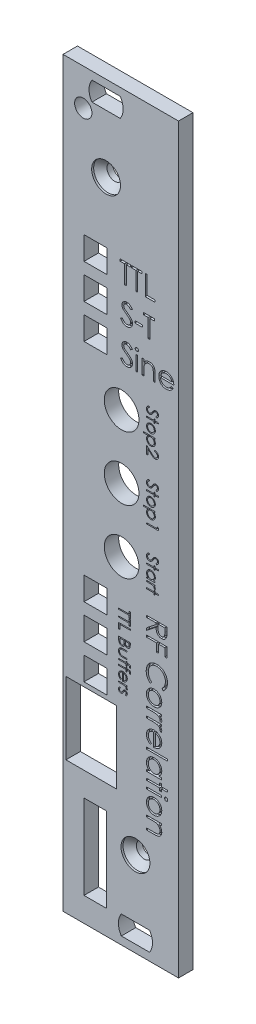
SolidWorks part; units mm, degrees
ref_plane "Front Plane" through (0, 0, 0) normal (0, 0, 1) x (1, 0, 0)
ref_plane "Top Plane" through (0, 0, 0) normal (0, 1, 0) x (1, 0, 0)
ref_plane "Right Plane" through (0, 0, 0) normal (1, 0, 0) x (0, 0, -1)
ref_plane "Plane1" through (0, 0, 2.5) normal (0, 0, 1) x (1, 0, 0)
sketch "Sketch1" plane through (0, 0, 2.5) normal (0, 0, 1) x (1, 0, 0)
  line L0 (12.53, 125.4) -> (-7.45, 125.4)
  line L1 (-7.45, 125.4) -> (-7.45, -3)
  line L2 (-7.45, -3) -> (12.53, -3)
  line L3 (12.53, -3) -> (12.53, 125.4)
extrude "Boss-Extrude1" add sketch "Sketch1" against normal blind 2.5
sketch "Sketch2" plane through (0, 0, 2.5) normal (0, 0, 1) x (1, 0, 0)
  line L0 (2.4454, 124.05) -> (-2.4454, 124.05)
  line L1 (-2.4454, 120.75) -> (2.4454, 120.75)
  arc A0 (-2.4454, 124.05) -> (-2.4454, 120.75) centre (0, 122.4) ccw
  arc A1 (2.4454, 120.75) -> (2.4454, 124.05) centre (0, 122.4) ccw
extrude "Cut-Extrude1" cut sketch "Sketch2" against normal through all
sketch "Sketch3" plane through (0, 0, 2.5) normal (0, 0, 1) x (1, 0, 0)
  line L0 (7.5254, 1.65) -> (2.6346, 1.65)
  line L1 (2.6346, -1.65) -> (7.5254, -1.65)
  arc A0 (2.6346, 1.65) -> (2.6346, -1.65) centre (5.08, 0) ccw
  arc A1 (7.5254, -1.65) -> (7.5254, 1.65) centre (5.08, 0) ccw
extrude "Cut-Extrude2" cut sketch "Sketch3" against normal through all
sketch "Sketch4" plane through (0, 0, 0) normal (0, 0, -1) x (-1, 0, 0)
  line L0 (3.82, 15.8) -> (-0.08, 15.8)
  line L1 (-0.08, 15.8) -> (-0.08, 1.2)
  line L2 (-0.08, 1.2) -> (3.82, 1.2)
  line L3 (3.82, 1.2) -> (3.82, 15.8)
extrude "Cut-Extrude3" cut sketch "Sketch4" against normal through all
hole_wizard "Ø3.0 (3) Diameter Hole1" positions "Sketch6" profile "Sketch5" hole size "Ø3.0" standard "ANSI Metric"
sketch "Sketch6" plane through (0, 0, 2.5) normal (0, 0, 1) x (1, 0, 0)
  point P0 (-3.95, 119.1)
sketch "Sketch5" plane through (-3.95, 119.1, 2.5) normal (1, 0, 0) x (0, -1, 0)
  line L0 (0, 0) -> (0, 2.5)
  line L1 (0, 2.5) -> (1.5, 2.5)
  line L2 (1.5, 2.5) -> (1.5, 0)
  line L5 (1.5, 0) -> (0, 0)
  line L11 (0, -6.35) -> (0, 107.95) construction
  dimension "Thru Hole Dia." = 3
  dimension "Thru Hole Depth" = 2.5
hole_wizard "CSK for M2.5 Flat Head Machine Screw1" positions "Sketch8" profile "Sketch7" countersink size "M2.5" standard "ANSI Metric"
sketch "Sketch8" plane through (0, 0, 2.5) normal (0, 0, 1) x (1, 0, 0)
  point P0 (5.08, 11.7)
  point P1 (0, 110.7)
sketch "Sketch7" plane through (5.08, 11.7, 2.5) normal (1, 0, 0) x (0, -1, 0)
  line L0 (0, 0) -> (0, 2.5)
  line L1 (0, 2.5) -> (1.35, 2.5)
  line L2 (1.35, 2.5) -> (1.35, 1.5)
  line L3 (1.35, 1.5) -> (2.5, 0.35)
  line L4 (2.5, 0.35) -> (2.5, 0)
  line L6 (2.5, 0) -> (0, 0)
  line L7 (-1.35, 1.5) -> (-2.5, 0.35) construction
  line L11 (0, -6.35) -> (0, 107.95) construction
  dimension "Thru Hole Dia." = 2.7
  dimension "Thru Hole Depth" = 2.5
  dimension "C'Sink Dia." = 5
  dimension "C'Sink Angle" = 90
  dimension "Head Clearance" = 0.35
ref_plane "Board bottom" through (0, 11.2, 0) normal (0, -1, 0) x (-1, 0, 0)
ref_plane "Board top" through (0, 111.2, 0) normal (0, 1, 0) x (1, 0, 0)
ref_plane "Board upper surface" through (-3.82, 0, 0) normal (1, 0, 0) x (0, 0, -1)
ref_plane "Board lower surface" through (-5.42, 0, 0) normal (1, 0, 0) x (0, 0, -1)
sketch "Sketch9" plane through (0, 0, 2.5) normal (0, 0, 1) x (1, 0, 0)
  line L0 (-3.82, 19.95) -> (-3.82, 32.45) construction
  line L1 (-3.82, 19.95) -> (1.78, 19.95)
  line L2 (-3.82, 32.45) -> (1.78, 32.45)
  line L3 (1.78, 19.95) -> (1.78, 32.45)
  line L4 (-3.82, -47.3899) -> (-3.82, 47.3899) construction
  line L5 (-28.8918, 11.2) -> (28.8918, 11.2) construction
  line L6 (-3.82, 32.45) -> (-3.82, 19.95) construction
  line L7 (-3.82, 32.45) -> (-6.95, 32.45)
  line L8 (-3.82, 19.95) -> (-6.95, 19.95)
  line L9 (-6.95, 32.45) -> (-6.95, 19.95)
  line L10 (-6.95, 32.45) -> (1.78, 19.95) construction
  line L11 (1.78, 32.45) -> (-6.95, 19.95) construction
  line L12 (-7.45, 125.4) -> (-7.45, -3) construction
  point P8 (-2.585, 26.2)
  dimension "D1" = 8.75
  dimension "D2" = 21.25
  dimension "D3" = 5.6
  dimension "D4" = 3.13
  dimension "D5" = 15
  dimension "D6" = 1.235
  dimension "D7" = 12.5
  dimension "D8" = 8.73
  dimension "D9" = 0.5
extrude "USB" cut sketch "Sketch9" against normal through all
sketch "Sketch10" plane through (0, 0, 2.5) normal (0, 0, 1) x (1, 0, 0)
  line L1 (-3.82, 37.2) -> (0.18, 37.2)
  line L2 (-3.82, 37.2) -> (-3.82, 33.2)
  line L3 (-3.82, 33.2) -> (0.18, 33.2)
  line L4 (0.18, 37.2) -> (0.18, 33.2)
  line L5 (-3.82, 37.2) -> (0.18, 33.2) construction
  line L6 (-3.82, 33.2) -> (0.18, 37.2) construction
  line L7 (-3.82, -47.3899) -> (-3.82, 47.3899) construction
  line L8 (-1.82, 35.2) -> (0.18, 35.2) construction
  line L9 (-28.8918, 11.2) -> (28.8918, 11.2) construction
  point P0 (-1.82, 35.2)
  dimension "D1" = 4
  dimension "D2" = 4
  dimension "D3" = 24
  dimension "D4" = 0
extrude "MCXX" cut sketch "Sketch10" against normal through all
pattern_linear "Copy MMCX 1" count 3 spacing 6 along (0, 1, 0) of "MCXX"
pattern_linear "Copy MMCX 2" count 2 spacing 51 along (0, 1, 0) of "Copy MMCX 1"
sketch "Sketch12" plane through (0, 0, 2.5) normal (0, 0, 1) x (1, 0, 0)
  line L0 (-3.82, -47.3899) -> (-3.82, 47.3899) construction
  line L1 (-28.8918, 11.2) -> (28.8918, 11.2) construction
  circle A0 centre (2.68, 55.2) radius 3
  dimension "D1" = 6
  dimension "D2" = 6.5
  dimension "D3" = 44
extrude "Selector 1" cut sketch "Sketch12" against normal through all
pattern_linear "Copy selector" count 3 spacing 11 along (0, 1, 0) of "Selector 1"
sketch "Sketch13" plane through (0, 0, 2.5) normal (0, 0, 1) x (1, 0, 0)
  line L0 (-3.82, 96.2) -> (0.18, 96.2) construction
  line L1 (0.18, 96.2) -> (0.18, 100.2) construction
  text T0 "TTL"
  dimension "D1" = 2.2
extrude "Text TTL" cut sketch "Sketch13" against normal blind 0.5
sketch "Sketch14" plane through (0, 0, 2.5) normal (0, 0, 1) x (1, 0, 0)
  line L7 (-3.82, 90.2) -> (0.18, 90.2) construction
  line L8 (2.4249, 99.341) -> (2.4249, 99.7) construction
  text T0 "S-T"
extrude "Text ST" cut sketch "Sketch14" against normal blind 0.5
sketch "Sketch15" plane through (0, 0, 2.5) normal (0, 0, 1) x (1, 0, 0)
  line L0 (-3.82, 84.2) -> (0.18, 84.2) construction
  line L1 (2.4249, 99.341) -> (2.4249, 99.7) construction
  text T0 "Sine"
extrude "Text Sine" cut sketch "Sketch15" against normal blind 0.5
ref_plane "Text align 2" through (7.03, 0, 0) normal (1, 0, 0) x (0, 0, -1)
sketch "Sketch17" plane through (0, 0, 2.5) normal (0, 0, 1) x (1, 0, 0)
  line L1 (2.68, 69.2) -> (7.03, 69.2) construction
  line L2 (7.03, -1.375) -> (7.03, 1.375) construction
  line L3 (7.03, 69.2) -> (7.03, 59.5505) construction
  circle A0 centre (2.68, 66.2) radius 3 construction
  text T0 "Stop1" font "Century Gothic" height 2
extrude "Cut-Extrude11" cut sketch "Sketch17" against normal blind 0.5
sketch "Sketch18" plane through (0, 0, 2.5) normal (0, 0, 1) x (1, 0, 0)
  line L0 (2.68, 58.2) -> (7.03, 58.2) construction
  line L1 (7.03, -1.375) -> (7.03, 1.375) construction
  line L2 (7.03, 58.2) -> (7.03, 47.8465) construction
  circle A0 centre (2.68, 55.2) radius 3 construction
  text T0 "Start" font "Century Gothic" height 2
extrude "Cut-Extrude12" cut sketch "Sketch18" against normal blind 0.5
sketch "Sketch21" plane through (0, 0, 2.5) normal (0, 0, 1) x (1, 0, 0)
  line L0 (2.68, 80.2) -> (7.03, 80.2) construction
  line L1 (7.03, -1.375) -> (7.03, 1.375) construction
  line L2 (7.03, 80.2) -> (7.03, 70.7585) construction
  circle A0 centre (2.68, 77.2) radius 3 construction
  text T0 "Stop2" font "Century Gothic" height 2
extrude "Cut-Extrude14" cut sketch "Sketch21" against normal blind 0.5
sketch "Sketch23" plane through (0, 0, 2.5) normal (0, 0, 1) x (1, 0, 0)
  line L0 (2.18, 49.2) -> (2.18, 33.2) construction
  line L1 (0.18, 33.2) -> (0.18, 37.2) construction
  line L2 (-3.82, 33.2) -> (0.18, 33.2) construction
  line L3 (0.18, 49.2) -> (-3.82, 49.2) construction
  line L4 (0.18, 39.2) -> (0.18, 43.2) construction
  text T0 "TTL Buffers" font "Century Gothic" height 2
  dimension "D1" = 2
extrude "Cut-Extrude15" cut sketch "Sketch23" against normal blind 0.5
sketch "Sketch24" plane through (0, 0, 2.5) normal (0, 0, 1) x (1, 0, 0)
  line L0 (7.03, 49.2) -> (7.03, 15.9676) construction
  line L1 (7.03, -1.375) -> (7.03, 1.375) construction
  line L2 (0.18, 49.2) -> (-3.82, 49.2) construction
  text T0 "RF Correlation"
extrude "Main title" cut sketch "Sketch24" against normal blind 0.5
equation "\"D6@Sketch9\"=2.47/2"
